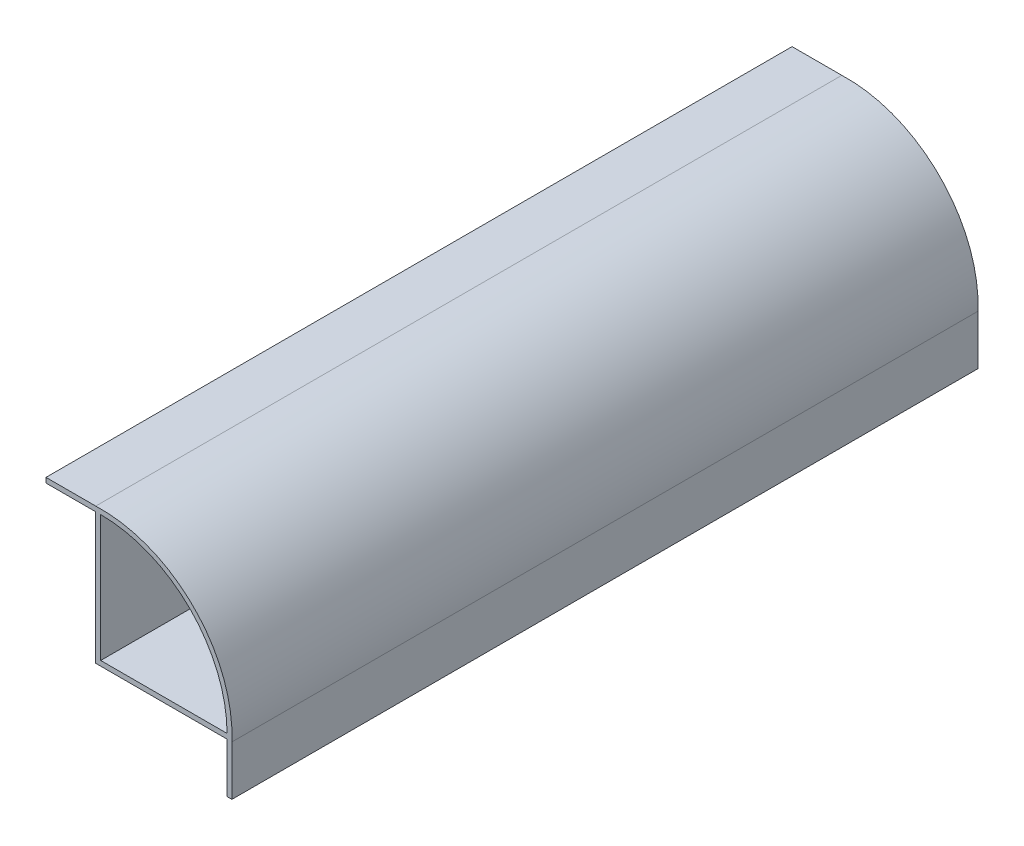
SolidWorks part; units mm, degrees
ref_plane "Alzado" through (0, 0, 0) normal (0, 0, 1) x (1, 0, 0)
ref_plane "Planta" through (0, 0, 0) normal (0, 1, 0) x (1, 0, 0)
ref_plane "Vista lateral" through (0, 0, 0) normal (1, 0, 0) x (0, 0, -1)
sketch "Croquis1" plane through (0, 0, 0) normal (0, 0, 1) x (1, 0, 0)
  line L0 (-13.7, -13.7) -> (13.6811, -13.7)
  line L1 (-12.7, -12.7) -> (12.7, -12.7)
  line L2 (-12.7, -12.7) -> (-12.7, 12.7)
  line L5 (0, 16.5842) -> (0, -23.118) construction
  line L6 (-13.7, -13.7) -> (-13.7, 13.6811)
  line L8 (-18.0998, 0) -> (17.5647, 0) construction
  line L9 (13.6811, -13.7) -> (12.6811, -13.7)
  line L10 (13.6811, -13.7) -> (13.6811, -23.7)
  line L11 (13.6811, -23.7) -> (12.6811, -23.7)
  line L12 (12.6811, -13.7) -> (12.6811, -23.7)
  line L13 (-13.7, 13.6811) -> (-23.7, 13.6811)
  line L14 (-13.7, 13.6811) -> (-13.7, 12.6811)
  line L15 (-13.7, 12.6811) -> (-23.7, 12.6811)
  line L16 (-23.7, 13.6811) -> (-23.7, 12.6811)
  arc A0 (-12.7, 12.7) -> (12.7, -12.7) centre (-12.7, -12.7) cw
  arc A1 (-13.7, 13.6811) -> (13.6811, -13.7) centre (-12.7, -12.7) cw
  point P0 (0, 0)
  point P12 (-12.7, 0)
  point P13 (0, -12.7)
  dimension "D3" = 25.4
  dimension "D1" = 25.4
  dimension "D2" = 25.4
  dimension "D5" = 1
  dimension "D6" = 10
  dimension "D7" = 1
  dimension "D8" = 10
  dimension "D4" = 1
extrude "Saliente-Extruir1" add sketch "Croquis1" along normal mid plane 150 contours A1 L6 L0 L2 A0 L1 | L13 L16 L15 L6 | L0 L12 L11 L10 region at (-13.3125, -0.5095, 0) region at (13.1811, -18.7, 0) region at (-18.7, 13.1811, 0)
ref_plane "Plano1" through (-12.7, -12.7, 75) normal (0, 1, 0) x (1, 0, 0)
